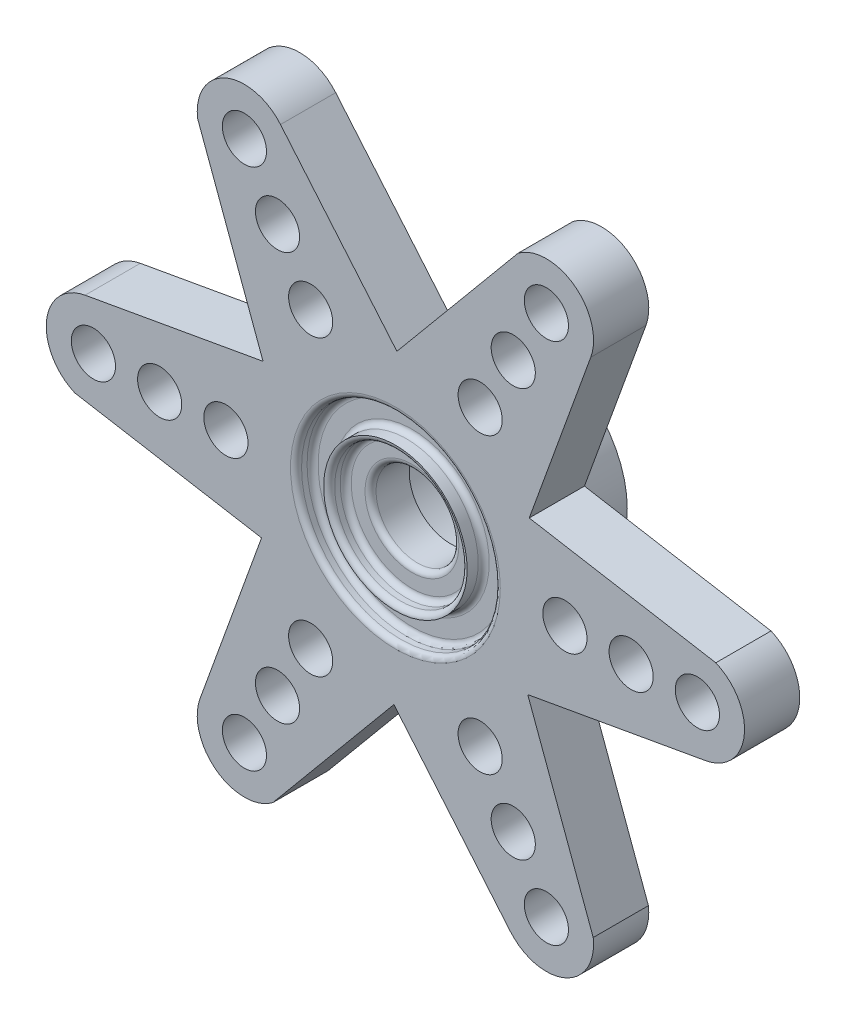
SolidWorks part; units mm, degrees
material "ABS PC"
ref_plane "Front Plane" through (0, 0, 0) normal (0, 0, 1) x (1, 0, 0)
ref_plane "Top Plane" through (0, 0, 0) normal (0, 1, 0) x (1, 0, 0)
ref_plane "Right Plane" through (0, 0, 0) normal (1, 0, 0) x (0, 0, -1)
sketch "Sketch1" plane through (0, 0, 0) normal (0, 0, 1) x (1, 0, 0)
  line L0 (0, 0) -> (7.675, 0) construction
  line L1 (7.675, 0) -> (10.675, 0) construction
  line L2 (10.675, 0) -> (13.675, 0) construction
  line L3 (0, 0) -> (3.8375, -6.6467) construction
  line L4 (3.8375, -6.6467) -> (5.3375, -9.2448) construction
  line L5 (5.3375, -9.2448) -> (6.8375, -11.8429) construction
  line L6 (0, 0) -> (-3.8375, -6.6467) construction
  line L7 (-3.8375, -6.6467) -> (-5.3375, -9.2448) construction
  line L8 (-5.3375, -9.2448) -> (-6.8375, -11.8429) construction
  line L9 (0, 0) -> (-7.675, 0) construction
  line L10 (-7.675, 0) -> (-10.675, 0) construction
  line L11 (-10.675, 0) -> (-13.675, 0) construction
  line L12 (0, 0) -> (-3.8375, 6.6467) construction
  line L13 (-3.8375, 6.6467) -> (-5.3375, 9.2448) construction
  line L14 (-5.3375, 9.2448) -> (-6.8375, 11.8429) construction
  line L15 (0, 0) -> (3.8375, 6.6467) construction
  line L16 (3.8375, 6.6467) -> (5.3375, 9.2448) construction
  line L17 (5.3375, 9.2448) -> (6.8375, 11.8429) construction
  line L18 (13.675, 0) -> (15.8115, 0) construction
  line L19 (7.675, 0) -> (7.9013, 3.1041) construction
  line L20 (7.675, 0) -> (6.7893, -3.3969) construction
  line L21 (7.9013, 3.1041) -> (14.5104, 1.9664)
  line L22 (6.7893, -3.3969) -> (14.0497, -2.1033)
  line L23 (0.4529, -7.5782) -> (5.2033, -13.2191)
  line L24 (6.6389, -5.2907) -> (8.9581, -11.5832)
  line L25 (-6.3364, -4.1813) -> (-8.8464, -11.1158)
  line L26 (-1.2624, -8.3948) -> (-5.5523, -13.5496)
  line L27 (-6.7893, 3.3969) -> (-14.0497, 2.1033)
  line L28 (-7.9013, -3.1041) -> (-14.5104, -1.9664)
  line L29 (-0.4529, 7.5782) -> (-5.2033, 13.2191)
  line L30 (-6.6389, 5.2907) -> (-8.9581, 11.5832)
  line L31 (6.3364, 4.1813) -> (8.8464, 11.1158)
  line L32 (1.2624, 8.3948) -> (5.5523, 13.5496)
  line L33 (-6.7893, 3.3969) -> (-5.9932, 3.5387)
  line L34 (-6.6389, 5.2907) -> (-5.9932, 3.5387)
  line L35 (-7.9013, -3.1041) -> (-6.0612, -3.4209)
  line L36 (-6.3364, -4.1813) -> (-6.0612, -3.4209)
  line L37 (0.4529, -7.5782) -> (-0.068, -6.9596)
  line L38 (7.9013, 3.1041) -> (6.0612, 3.4209)
  line L39 (6.7893, -3.3969) -> (5.9932, -3.5387)
  line L40 (-1.2624, -8.3948) -> (-0.068, -6.9596)
  line L41 (6.6389, -5.2907) -> (5.9932, -3.5387)
  line L42 (6.3364, 4.1813) -> (6.0612, 3.4209)
  line L43 (-0.4529, 7.5782) -> (0.068, 6.9596)
  line L44 (1.2624, 8.3948) -> (0.068, 6.9596)
  circle A0 centre (7.675, 0) radius 1
  circle A1 centre (10.675, 0) radius 1
  circle A2 centre (13.675, 0) radius 1
  circle A3 centre (3.8375, -6.6467) radius 1
  circle A4 centre (5.3375, -9.2448) radius 1
  circle A5 centre (6.8375, -11.8429) radius 1
  circle A6 centre (-3.8375, -6.6467) radius 1
  circle A7 centre (-5.3375, -9.2448) radius 1
  circle A8 centre (-6.8375, -11.8429) radius 1
  circle A9 centre (-7.675, 0) radius 1
  circle A10 centre (-10.675, 0) radius 1
  circle A11 centre (-13.675, 0) radius 1
  circle A12 centre (-3.8375, 6.6467) radius 1
  circle A13 centre (-5.3375, 9.2448) radius 1
  circle A14 centre (-6.8375, 11.8429) radius 1
  circle A15 centre (3.8375, 6.6467) radius 1
  circle A16 centre (5.3375, 9.2448) radius 1
  circle A17 centre (6.8375, 11.8429) radius 1
  arc A18 (14.0497, -2.1033) -> (14.5104, 1.9664) centre (13.675, 0) ccw
  arc A19 (5.2033, -13.2191) -> (8.9581, -11.5832) centre (6.8375, -11.8429) ccw
  arc A20 (-8.8464, -11.1158) -> (-5.5523, -13.5496) centre (-6.8375, -11.8429) ccw
  arc A21 (-14.0497, 2.1033) -> (-14.5104, -1.9664) centre (-13.675, 0) ccw
  arc A22 (-5.2033, 13.2191) -> (-8.9581, 11.5832) centre (-6.8375, 11.8429) ccw
  arc A23 (8.8464, 11.1158) -> (5.5523, 13.5496) centre (6.8375, 11.8429) ccw
  circle A24 centre (0, 0) radius 1.875
  point P40 (0, 0)
  point P74 (0, 0)
  point P76 (0, 0)
  point P99 (0, 0)
  dimension "D3" = 2
  dimension "D2" = 3.75
  dimension "D1" = 7.675
  dimension "D5" = 3
  dimension "D6" = 3
  dimension "D7" = 13.675
  dimension "D8" = 6
  dimension "D10" = 2.1365
  dimension "D4" = 6
extrude "Boss-Extrude1" add sketch "Sketch1" along normal blind 2.5
sketch "Sketch2" plane through (0, 0, 2.5) normal (0, 0, 1) x (1, 0, 0)
  circle A0 centre (0, 0) radius 3
  circle A1 centre (0, 0) radius 4.5
  circle A2 centre (0, 0) radius 3.25
  circle A3 centre (0, 0) radius 1.875
  circle M37 centre (0, 0) radius 1.875
  dimension "D1" = 6
  dimension "D2" = 9
  dimension "D3" = 6.5
extrude "Cut-Extrude1" cut sketch "Sketch2" against normal blind 0.75 contours A0 M37 | A1 A2 region at (-2.9151, 0, 2.5) region at (-4.3727, 0, 2.5)
fillet "Fillet2" radius 0.25 6 edges at (1.875, 0, 1.75) (3.25, 0, 1.75) (3, 0, 1.75) (4.5, 0, 1.75) (3, 0, 2.5) (4.5, 0, 2.5)
sketch "Sketch3" plane through (0, 0, 0) normal (0, 0, -1) x (-1, 0, 0)
  circle A0 centre (0, 0) radius 4.5
  circle A1 centre (0, 0) radius 3.625
  dimension "D1" = 9
  dimension "D2" = 7.25
extrude "Boss-Extrude2" add sketch "Sketch3" along normal blind 3.5
